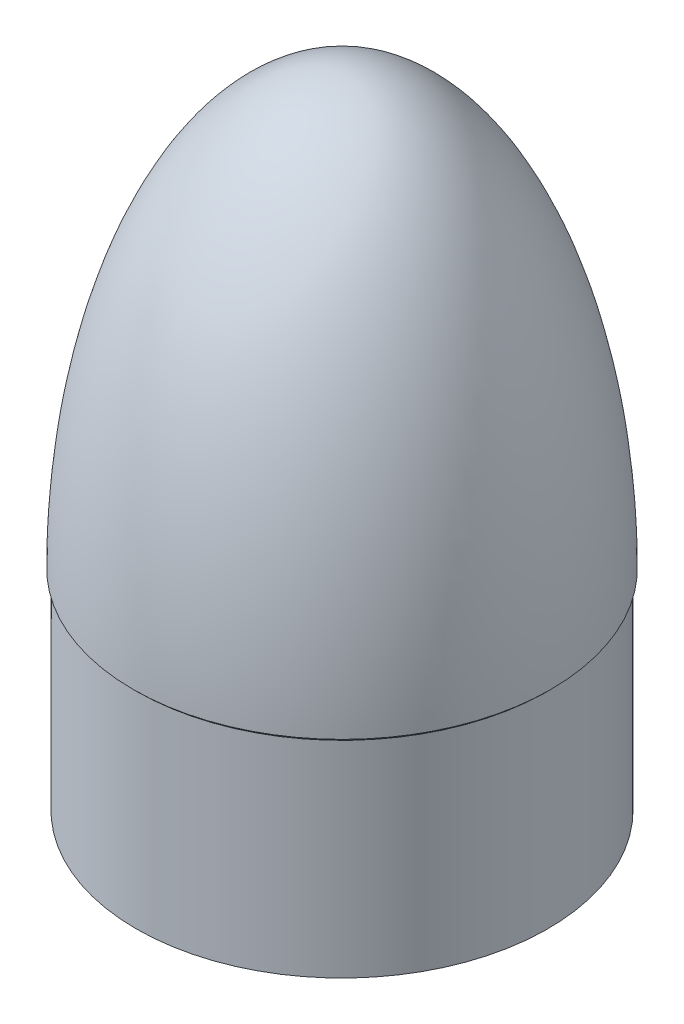
SolidWorks part; units mm, degrees
ref_plane "Front Plane" through (0, 0, 0) normal (0, 0, 1) x (1, 0, 0)
ref_plane "Top Plane" through (0, 0, 0) normal (0, 1, 0) x (1, 0, 0)
ref_plane "Right Plane" through (0, 0, 0) normal (1, 0, 0) x (0, 0, -1)
sketch "Sketch1" plane through (0, 0, 0) normal (0, 0, 1) x (1, 0, 0)
  line L3 (0, 0) -> (0, 202.3003) construction
  line L5 (0, 165.1) -> (0, 162.1028)
  line L12 (76.3778, -80.518) -> (79.375, -80.518)
  line L13 (79.375, -80.518) -> (79.375, -1.143)
  line L14 (80.518, 0) -> (79.375, -1.143)
  line L15 (79.375, -1.143) -> (80.518, -1.143) construction
  line L17 (76.3778, 0.1703) -> (76.3778, -80.518)
  line L18 (76.3778, 0.1703) -> (77.4677, 1.2602)
  line L19 (77.47, 0) -> (76.3778, -1.0922) construction
  ellipse E0 centre (0, 0) end of major axis (0, 162.1028) minor radius 77.47 (77.4677, 1.2602) -> (0, 162.1028) ccw
  ellipse E1 centre (0, 0) end of major axis (0, -165.1) minor radius 80.518 (80.518, 0) -> (0, 165.1) ccw
  dimension "D1" = 158.75
  dimension "D2" = 79.375
  dimension "D3" = 165.1
  dimension "D4" = 161.036
  dimension "D5" = 2.9972
  dimension "D6" = 2.9972
  dimension "D7" = 45
  dimension "D8" = 3.048
  dimension "D9" = 3.048
revolve "Revolve1" add sketch "Sketch1" angle 360 about L5
